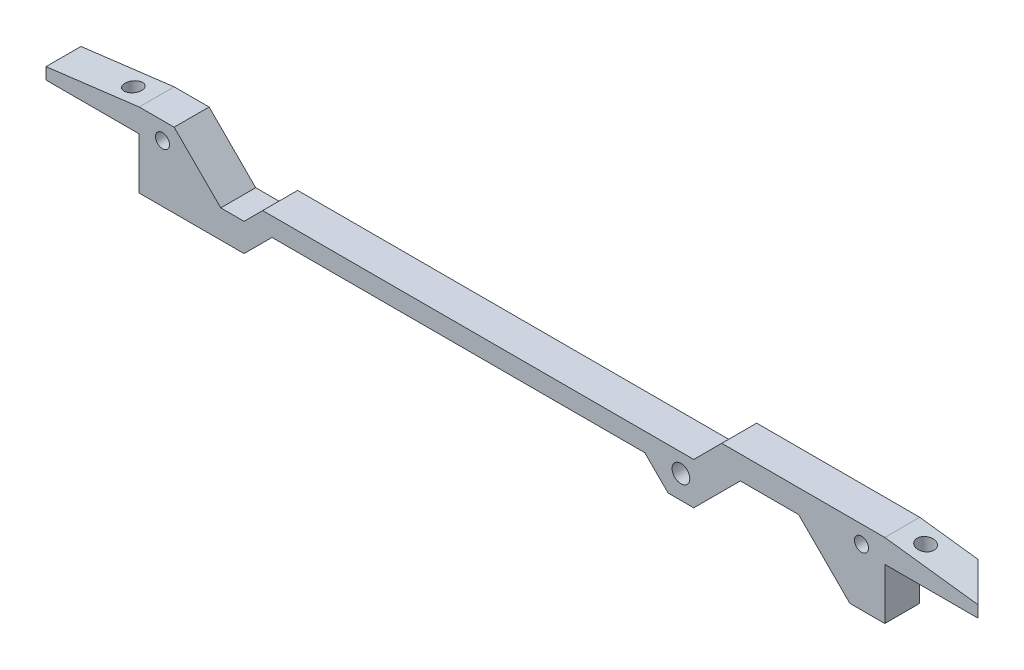
SolidWorks part; units mm, degrees
ref_plane "Front Plane" through (0, 0, 0) normal (0, 0, 1) x (1, 0, 0)
ref_plane "Top Plane" through (0, 0, 0) normal (0, 1, 0) x (1, 0, 0)
ref_plane "Right Plane" through (0, 0, 0) normal (1, 0, 0) x (0, 0, -1)
sketch "Sketch1" plane through (0, 0, 0) normal (0, 0, 1) x (1, 0, 0)
  line L0 (0, 12.7) -> (25.4, 12.7)
  line L5 (25.4, 12.7) -> (25.4, -1.27)
  line L6 (25.4, -1.27) -> (53.975, -1.27)
  line L7 (228.6, -1.27) -> (228.6, 12.7)
  line L10 (53.975, -1.27) -> (61.595, 6.35)
  line L12 (228.6, 19.05) -> (184.15, 19.05)
  line L13 (25.4, 19.05) -> (0, 15.875)
  line L14 (0, 15.875) -> (0, 12.7)
  line L15 (61.595, 6.35) -> (163.195, 6.35)
  line L18 (184.15, 19.05) -> (176.53, 11.43)
  line L19 (176.53, 11.43) -> (59.055, 11.43)
  line L20 (47.625, 6.35) -> (34.925, 19.05)
  line L21 (176.53, 0) -> (189.23, 12.7)
  line L22 (189.23, 12.7) -> (205.105, 12.7)
  line L23 (205.105, 12.7) -> (219.075, -1.27)
  line L24 (219.075, -1.27) -> (228.6, -1.27)
  line L25 (169.545, 0) -> (176.53, 0)
  line L26 (34.925, 19.05) -> (25.4, 19.05)
  line L28 (169.545, 0) -> (163.195, 6.35)
  line L29 (228.6, 19.05) -> (254, 15.875)
  line L30 (254, 15.875) -> (254, 12.7)
  line L31 (254, 12.7) -> (228.6, 12.7)
  line L33 (53.975, 6.35) -> (47.625, 6.35)
  line L34 (59.055, 11.43) -> (53.975, 6.35)
  point P20 (50.8, 6.35)
  point P29 (173.0375, 0)
  dimension "D1" = 12.7
  dimension "D2" = 25.4
  dimension "D3" = 228.6
  dimension "D4" = 6.35
  dimension "D5" = 28.575
  dimension "D6" = 12.7
  dimension "D7" = 15.875
  dimension "D8" = 12.7
  dimension "D9" = 1.27
  dimension "D10" = 3.175
  dimension "D11" = 9.525
  dimension "D12" = 9.525
  dimension "D13" = 6.35
  dimension "D14" = 44.45
  dimension "D15" = 25.4
  dimension "D16" = 13.97
  dimension "D17" = 3.175
  dimension "D18" = 45
  dimension "D19" = 6.35
  dimension "D20" = 25.4
  dimension "D21" = 55.5625
  dimension "D22" = 1.27
extrude "Boss-Extrude1" add sketch "Sketch1" against normal blind 9.525
sketch "Sketch2" plane through (0, 0, 0) normal (0, 0, 1) x (1, 0, 0)
  line L0 (228.6, 19.05) -> (184.15, 19.05) construction
  line L1 (25.4, 12.7) -> (25.4, -1.27) construction
  line L2 (228.6, -1.27) -> (228.6, 12.7) construction
  circle A0 centre (31.75, 14.2875) radius 1.905
  circle A1 centre (95.25, 14.2875) radius 1.905
  circle A2 centre (158.75, 14.2875) radius 1.905
  circle A3 centre (222.25, 14.2875) radius 1.905
  circle A6 centre (173.0375, 6.35) radius 2.413
  circle A7 centre (173.0375, 6.35) radius 2.413
  dimension "D1" = 3.81
  dimension "D2" = 4.7625
  dimension "D3" = 6.35
  dimension "D5" = 6.35
  dimension "D6" = 0.381
  dimension "D4" = 4
extrude "Cut-Extrude2" cut sketch "Sketch2" against normal through all
chamfer "Chamfer1" distance 9.525 angle 45 1 edges at (254, 14.2875, -9.525)
sketch "Sketch4" plane through (0, 12.7, 0) normal (0, -1, 0) x (-1, 0, 0)
  line L1 (-228.6, 9.525) -> (-228.6, 0) construction
  line L2 (-25.4, 9.525) -> (-25.4, 0) construction
  circle A0 centre (-234.95, 4.7652) radius 2.286
  circle A1 centre (-19.05, 4.7652) radius 2.286
  point P8 (0, 0)
  point P9 (-19.05, 4.7652)
  point P10 (0, 0)
  dimension "D2" = 4.572
  dimension "D1" = 6.35
  dimension "D3" = 6.35
extrude "Cut-Extrude4" cut sketch "Sketch4" against normal up to next
